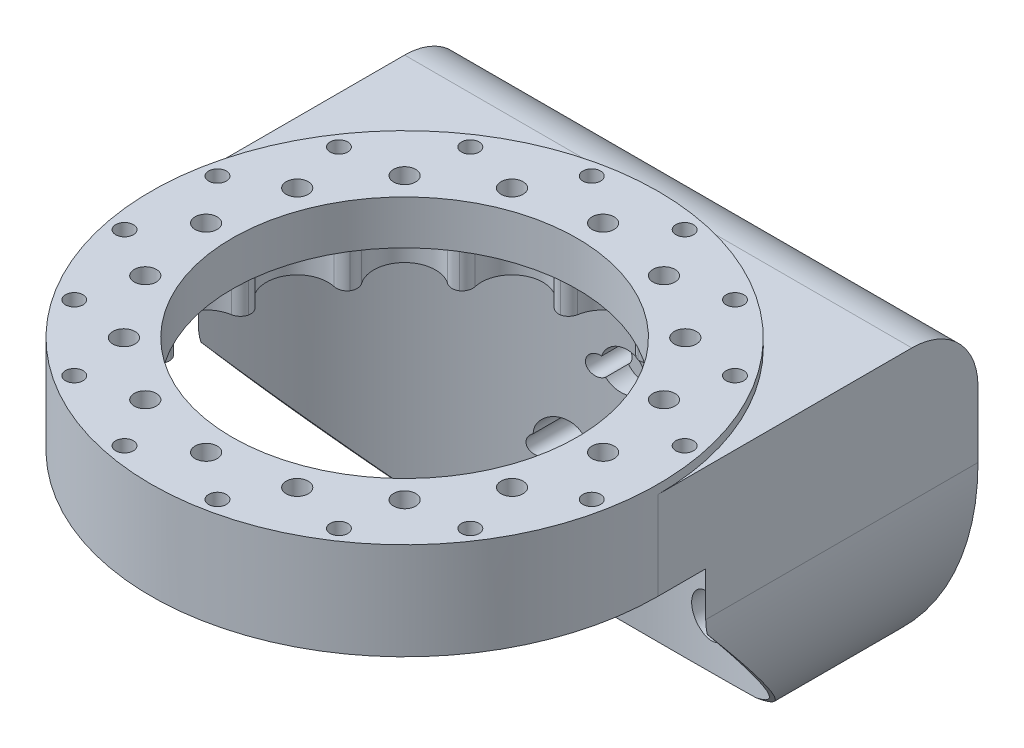
SolidWorks part; units mm, degrees
ref_plane "Front Plane" through (0, 0, 0) normal (0, 0, 1) x (1, 0, 0)
ref_plane "Top Plane" through (0, 0, 0) normal (0, 1, 0) x (1, 0, 0)
ref_plane "Right Plane" through (0, 0, 0) normal (1, 0, 0) x (0, 0, -1)
sketch "Sketch1" plane through (0, 0, 0) normal (0, 1, 0) x (1, 0, 0)
  line L0 (-10.5349, 52.9624) -> (0, 0) construction
  line L1 (0, 0) -> (24.6214, 0) construction
  circle A12 centre (0, 0) radius 39.1
  circle A13 centre (0, 0) radius 57.5
  circle A14 centre (0, 0) radius 54 construction
  circle A15 centre (-10.5349, 52.9624) radius 2
  circle A16 centre (10.5349, 52.9624) radius 2
  circle A17 centre (30.0008, 44.8994) radius 2
  circle A18 centre (44.8994, 30.0008) radius 2
  circle A19 centre (52.9624, 10.5349) radius 2
  circle A20 centre (52.9624, -10.5349) radius 2
  circle A21 centre (44.8994, -30.0008) radius 2
  circle A22 centre (30.0008, -44.8994) radius 2
  circle A23 centre (10.5349, -52.9624) radius 2
  circle A24 centre (-10.5349, -52.9624) radius 2
  circle A25 centre (-30.0008, -44.8994) radius 2
  circle A26 centre (-44.8994, -30.0008) radius 2
  circle A47 centre (-52.9624, -10.5349) radius 2
  circle A48 centre (-52.9624, 10.5349) radius 2
  circle A49 centre (-44.8994, 30.0008) radius 2
  circle A50 centre (-30.0008, 44.8994) radius 2
  point P21 (0, 0)
  point P28 (0, 0)
  point P56 (0, 0)
  point P60 (0, 0)
  dimension "D1" = 101.25
  dimension "D4" = 115
  dimension "D5" = 78.2
  dimension "D6" = 108
  dimension "D7" = 4
  dimension "D8" = 16
extrude "Boss-Extrude1" add sketch "Sketch1" along normal blind 10
sketch "Sketch2" plane through (0, 10, 0) normal (0, 1, 0) x (1, 0, 0)
  circle A0 centre (0, 0) radius 45 construction
  circle A1 centre (0, 45) radius 2.5
  circle A2 centre (17.2208, 41.5746) radius 2.5
  circle A3 centre (31.8198, 31.8198) radius 2.5
  circle A4 centre (41.5746, 17.2208) radius 2.5
  circle A5 centre (45, 0) radius 2.5
  circle A6 centre (41.5746, -17.2208) radius 2.5
  circle A7 centre (31.8198, -31.8198) radius 2.5
  circle A8 centre (17.2208, -41.5746) radius 2.5
  circle A9 centre (0, -45) radius 2.5
  circle A10 centre (-17.2208, -41.5746) radius 2.5
  circle A11 centre (-31.8198, -31.8198) radius 2.5
  circle A12 centre (-41.5746, -17.2208) radius 2.5
  circle A13 centre (-45, 0) radius 2.5
  circle A14 centre (-41.5746, 17.2208) radius 2.5
  circle A15 centre (-31.8198, 31.8198) radius 2.5
  circle A16 centre (-17.2208, 41.5746) radius 2.5
  point P27 (0, 0)
  dimension "D1" = 90
  dimension "D2" = 5
  dimension "D3" = 16
extrude "Cut-Extrude1" cut sketch "Sketch2" against normal blind 10
sketch "Sketch4" plane through (0, 0, 0) normal (0, 1, 0) x (1, 0, 0)
  circle A0 centre (0, 0) radius 45 construction
  circle A1 centre (0, 45) radius 5
  circle A2 centre (0, 45) radius 2.5
  circle A3 centre (17.2208, 41.5746) radius 2.5
  circle A4 centre (31.8198, 31.8198) radius 2.5
  circle A5 centre (41.5746, 17.2208) radius 2.5
  circle A6 centre (45, 0) radius 2.5
  circle A7 centre (41.5746, -17.2208) radius 2.5
  circle A8 centre (31.8198, -31.8198) radius 2.5
  circle A9 centre (17.2208, -41.5746) radius 2.5
  circle A10 centre (0, -45) radius 2.5
  circle A11 centre (-17.2208, -41.5746) radius 2.5
  circle A12 centre (-31.8198, -31.8198) radius 2.5
  circle A13 centre (17.2208, 41.5746) radius 5
  circle A14 centre (31.8198, 31.8198) radius 5
  circle A15 centre (41.5746, 17.2208) radius 5
  circle A16 centre (45, 0) radius 5
  circle A17 centre (41.5746, -17.2208) radius 5
  circle A18 centre (31.8198, -31.8198) radius 5
  circle A19 centre (17.2208, -41.5746) radius 5
  circle A20 centre (0, -45) radius 5
  circle A21 centre (-17.2208, -41.5746) radius 5
  circle A22 centre (-31.8198, -31.8198) radius 5
  circle A23 centre (-41.5746, -17.2208) radius 5
  circle A24 centre (-45, 0) radius 5
  circle A25 centre (-41.5746, 17.2208) radius 5
  circle A26 centre (-31.8198, 31.8198) radius 5
  circle A27 centre (-17.2208, 41.5746) radius 5
  circle A28 centre (-41.5746, -17.2208) radius 2.5
  circle A29 centre (-45, 0) radius 2.5
  circle A30 centre (-41.5746, 17.2208) radius 2.5
  circle A31 centre (-31.8198, 31.8198) radius 2.5
  circle A32 centre (-17.2208, 41.5746) radius 2.5
  point P29 (0, 0)
  point P50 (0, 0)
  dimension "D1" = 10
  dimension "D2" = 16
  dimension "D3" = 16
extrude "Boss-Extrude3" add sketch "Sketch4" against normal blind 0.4
sketch "Sketch5" plane through (0, 0, 0) normal (0, -1, 0) x (1, 0, 0)
  circle A0 centre (0, 0) radius 57.5
  circle A1 centre (0, 0) radius 45
  circle A2 centre (0, 45) radius 7
  circle A3 centre (17.2208, 41.5746) radius 7
  circle A4 centre (31.8198, 31.8198) radius 7
  circle A5 centre (41.5746, 17.2208) radius 7
  circle A6 centre (45, 0) radius 7
  circle A7 centre (41.5746, -17.2208) radius 7
  circle A8 centre (31.8198, -31.8198) radius 7
  circle A9 centre (17.2208, -41.5746) radius 7
  circle A10 centre (0, -45) radius 7
  circle A11 centre (-17.2208, -41.5746) radius 7
  circle A12 centre (-31.8198, -31.8198) radius 7
  circle A13 centre (-41.5746, -17.2208) radius 7
  circle A14 centre (-45, 0) radius 7
  circle A15 centre (-41.5746, 17.2208) radius 7
  circle A16 centre (-31.8198, 31.8198) radius 7
  circle A17 centre (-17.2208, 41.5746) radius 7
  circle A18 centre (0, 0) radius 54 construction
  circle A19 centre (-10.5349, 52.9624) radius 2
  circle A20 centre (10.5349, 52.9624) radius 2
  circle A21 centre (30.0008, 44.8994) radius 2
  circle A22 centre (44.8994, 30.0008) radius 2
  circle A23 centre (52.9624, 10.5349) radius 2
  circle A24 centre (52.9624, -10.5349) radius 2
  circle A25 centre (44.8994, -30.0008) radius 2
  circle A26 centre (30.0008, -44.8994) radius 2
  circle A27 centre (10.5349, -52.9624) radius 2
  circle A28 centre (-10.5349, -52.9624) radius 2
  circle A29 centre (-30.0008, -44.8994) radius 2
  circle A30 centre (-44.8994, -30.0008) radius 2
  circle A31 centre (-52.9624, -10.5349) radius 2
  circle A32 centre (-52.9624, 10.5349) radius 2
  circle A33 centre (-44.8994, 30.0008) radius 2
  circle A34 centre (-30.0008, 44.8994) radius 2
  point P39 (0, 0)
  point P75 (0, 0)
  circle M34 centre (0, 0) radius 57.5
  circle M35 centre (-52.9624, 10.5349) radius 2
  circle M37 centre (-52.9624, -10.5349) radius 2
  circle M39 centre (-30.0008, -44.8994) radius 2
  circle M41 centre (10.5349, -52.9624) radius 2
  circle M43 centre (44.8994, -30.0008) radius 2
  circle M45 centre (52.9624, 10.5349) radius 2
  circle M47 centre (30.0008, 44.8994) radius 2
  circle M49 centre (-10.5349, 52.9624) radius 2
  dimension "D1" = 14
  dimension "D2" = 16
  dimension "D3" = 16
extrude "Boss-Extrude4" add sketch "Sketch5" along normal blind 12 contours A17 A1 A2 A3 A4 A5 A6 A7 A8 A9 A10 A11 A12 A13 A14 A15 A16 M34 M35 M37 M39 M41 M43 M45 M47 M49 region at (-55.8737, 0, 0)
fillet "Fillet2" radius 2.5 32 edges at (-23.46, -6, -38.4009) (-26.5001, -6, -36.3696) (-6.9788, -6, -44.4556) (-10.5648, -6, -43.7422) (10.5648, -6, -43.7422) (6.9788, -6, -44.4556) (26.5001, -6, -36.3696) (23.46, -6, -38.4009) (38.4009, -6, -23.46) (36.3696, -6, -26.5001) (44.4556, -6, -6.9788) (43.7422, -6, -10.5648) (43.7422, -6, 10.5648) (44.4556, -6, 6.9788) (-38.4009, -6, -23.46) (-36.3696, -6, -26.5001) (-44.4556, -6, -6.9788) (-43.7422, -6, -10.5648) (-43.7422, -6, 10.5648) (-44.4556, -6, 6.9788) (-36.3696, -6, 26.5001) (-38.4009, -6, 23.46) (-23.46, -6, 38.4009) (-26.5001, -6, 36.3696) (-10.5648, -6, 43.7422) (-6.9788, -6, 44.4556) (6.9788, -6, 44.4556) (10.5648, -6, 43.7422) (23.46, -6, 38.4009) (26.5001, -6, 36.3696) (38.4009, -6, 23.46) (36.3696, -6, 26.5001)
sketch "Sketch6" plane through (0, -12, 0) normal (0, -1, 0) x (1, 0, 0)
  line L0 (-57.5, 0) -> (57.5, 0) construction
  line L1 (57.5, 0) -> (57.5, -57.5)
  line L2 (57.5, -57.5) -> (-57.5, -57.5)
  line L3 (-57.5, -57.5) -> (-57.5, 0)
  circle A0 centre (0, 0) radius 57.5 construction
  arc A1 (-57.5, 0) -> (57.5, 0) centre (0, 0) ccw
extrude "Boss-Extrude7" add sketch "Sketch6" against normal blind 20 contours A1 L2 L1 | A1 L3 L2 region at (-44.6563, -12, -44.6563) region at (44.6563, -12, -44.6563)
sketch "Sketch7" plane through (-57.5, 0, 0) normal (-1, 0, 0) x (0, 0, 1)
  line L0 (-57.5, 8) -> (-57.5, -79.5)
  line L1 (-57.5, -79.5) -> (-72.5, -79.5)
  line L2 (-72.5, -79.5) -> (-72.5, 8)
  line L3 (-72.5, 8) -> (-57.5, 8)
  line L4 (-57.5, -79.5) -> (0, -12)
  line L5 (0, -12) -> (-57.5, -12)
  line M5 (-57.5, -12) -> (0, -12)
  line M8 (-57.5, 8) -> (-57.5, -12)
  dimension "D1" = 15
  dimension "D2" = 87.5
  dimension "D3" = 67.5
extrude "Boss-Extrude8" add sketch "Sketch7" against normal blind 115 contours L3 L2 L1 L0 M8 | L0 L4 M5 region at (-57.5, -35.75, -65) region at (-57.5, -34.5, -38.3333)
sketch "Sketch8" plane through (0, -79.5, 0) normal (0, -1, 0) x (1, 0, 0)
  circle A0 centre (0, 0) radius 58.5
  dimension "D1" = 117
extrude "Cut-Extrude2" cut sketch "Sketch8" against normal blind 67.5
sketch "Sketch9" plane through (0, 0, -72.5) normal (0, 0, -1) x (-1, 0, 0)
  line L0 (0, 19.2611) -> (0, -105.8991) construction
  line L1 (-57.5, -79.5) -> (57.5, -79.5) construction
  circle A0 centre (0, -49.5) radius 30 construction
  circle A1 centre (0, -49.5) radius 23 construction
  circle A2 centre (23, -49.5) radius 2.25
  circle A3 centre (11.5, -67.4786) radius 2.25
  circle A4 centre (-9.8199, -66.5086) radius 2.25
  circle A5 centre (-19.6398, -47.56) radius 2.25
  circle A6 centre (-8.1398, -29.5814) radius 2.25
  circle A7 centre (13.1801, -30.5514) radius 2.25
  point P22 (1.6801, -48.53)
  dimension "D1" = 60
  dimension "D2" = 46
  dimension "D3" = 4.5
  dimension "D4" = 6
extrude "Cut-Extrude3" cut sketch "Sketch9" against normal blind 67.5
sketch "Sketch10" plane through (0, 0, 0) normal (0, 0, 1) x (1, 0, 0)
  line L0 (57.5, -79.5) -> (10.7703, -79.5) construction
  circle A0 centre (0, -49.5) radius 30 construction
  circle A1 centre (0, -49.5) radius 23 construction
  circle A2 centre (23, -49.5) radius 4.5
  circle A3 centre (11.5, -67.4786) radius 4.5
  circle A4 centre (-9.8199, -66.5086) radius 4.5
  circle A5 centre (-19.6398, -47.56) radius 4.5
  circle A6 centre (-8.1398, -29.5814) radius 4.5
  circle A7 centre (13.1801, -30.5514) radius 4.5
  point P19 (1.6801, -48.53)
  dimension "D1" = 60
  dimension "D2" = 46
  dimension "D3" = 9
  dimension "D4" = 6
extrude "Cut-Extrude4" cut sketch "Sketch10" against normal blind 62.5
sketch "Sketch11" plane through (0, 0, -72.5) normal (0, 0, -1) x (-1, 0, 0)
  line L0 (0, 13.9005) -> (0, -82.4311) construction
  line L1 (-57.5, -79.5) -> (57.5, -79.5) construction
  line L2 (-57.5, -22) -> (-57.5, -79.5)
  line L3 (-57.5, -79.5) -> (57.5, -79.5)
  line L4 (57.5, -79.5) -> (57.5, -20.06)
  circle A0 centre (0, -22) radius 57.5
  line M8 (57.5, -79.5) -> (57.5, 8)
  line M10 (-57.5, 8) -> (-57.5, -79.5)
  line M11 (-57.5, -79.5) -> (57.5, -79.5)
  dimension "D1" = 115
extrude "Cut-Extrude5" cut sketch "Sketch11" against normal blind 133 contours A0 M10 M11 | A0 L3 M8 region at (44.6563, -66.6563, -72.5) region at (-44.6563, -66.6563, -72.5)
fillet "Fillet4" radius 15 1 edges at (0, 8, -72.5)
